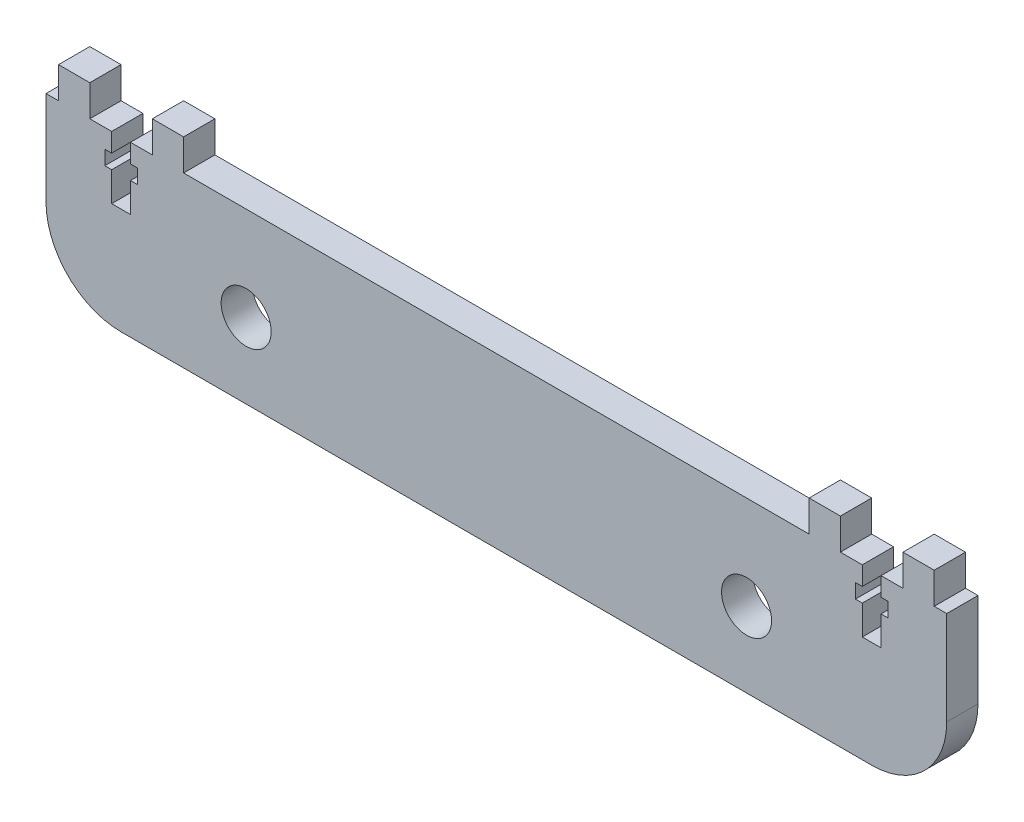
SolidWorks part; units mm, degrees
ref_plane "Front Plane" through (0, 0, 0) normal (0, 0, 1) x (1, 0, 0)
ref_plane "Top Plane" through (0, 0, 0) normal (0, 1, 0) x (1, 0, 0)
ref_plane "Right Plane" through (0, 0, 0) normal (1, 0, 0) x (0, 0, -1)
sketch "Sketch1" plane through (0, 0, 0) normal (0, 0, 1) x (1, 0, 0)
  line L0 (0, 0) -> (0, 77.1281) construction
  line L1 (0, 0) -> (-105.7988, 0) construction
  line L4 (-72, 0) -> (-72, 15)
  line L6 (-72, 15) -> (72, 15)
  line L7 (-60, -12) -> (60, -12)
  line L8 (72, 0) -> (72, 15)
  arc A1 (-72, 0) -> (-60, -12) centre (-60, 0) ccw
  circle A4 centre (-40, 0) radius 4
  circle A5 centre (40, 0) radius 4
  arc A6 (72, 0) -> (60, -12) centre (60, 0) cw
  point P12 (0, -12)
  point P13 (0, 15)
  point P14 (0, -12)
  point P15 (0, 15)
  line B0 (-57.4, 12) -> (-57.4, 9.7)
  line B1 (-61.5, 9.7) -> (-61.5, 5)
  line B2 (-58.5, 5) -> (-58.5, 9.7)
  line B3 (-57.4, 9.7) -> (-58.5, 9.7)
  line B4 (-60, 15) -> (-60, 3.7792) construction
  line B5 (-58.5, 15) -> (-55, 15)
  line B6 (-55, 20) -> (-50, 20)
  line B7 (-50, 20) -> (-50, 15)
  line B8 (-55, 20) -> (-55, 15)
  line B9 (-61.5, 15) -> (-65, 15)
  line B10 (-65, 15) -> (-65, 20)
  line B11 (-65, 20) -> (-70, 20)
  line B12 (-70, 20) -> (-70, 15)
  line B13 (-58.5, 15) -> (-61.5, 15) construction
  line B14 (-61.5, 15) -> (-61.5, 12)
  line B15 (-61.5, 9.7) -> (-62.6, 9.7)
  line B16 (-62.6, 12) -> (-61.5, 12)
  line B17 (-61.5, 5) -> (-58.5, 5)
  line B18 (-58.5, 12) -> (-57.4, 12)
  line B19 (-62.6, 9.7) -> (-62.6, 12)
  line B20 (-58.5, 12) -> (-58.5, 15)
  line B21 (-60, 5) -> (-60, 15) construction
  line B22 (57.4, 12) -> (57.4, 9.7)
  line B23 (61.5, 9.7) -> (61.5, 5)
  line B24 (58.5, 5) -> (58.5, 9.7)
  line B25 (57.4, 9.7) -> (58.5, 9.7)
  line B26 (60, 15) -> (60, 3.7792) construction
  line B27 (58.5, 15) -> (55, 15)
  line B28 (55, 20) -> (50, 20)
  line B29 (50, 20) -> (50, 15)
  line B30 (55, 20) -> (55, 15)
  line B31 (61.5, 15) -> (65, 15)
  line B32 (65, 15) -> (65, 20)
  line B33 (65, 20) -> (70, 20)
  line B34 (70, 20) -> (70, 15)
  line B35 (58.5, 15) -> (61.5, 15) construction
  line B36 (61.5, 15) -> (61.5, 12)
  line B37 (61.5, 9.7) -> (62.6, 9.7)
  line B38 (62.6, 12) -> (61.5, 12)
  line B39 (61.5, 5) -> (58.5, 5)
  line B40 (58.5, 12) -> (57.4, 12)
  line B41 (62.6, 9.7) -> (62.6, 12)
  line B42 (58.5, 12) -> (58.5, 15)
  line B43 (60, 5) -> (60, 15) construction
  dimension "D3" = 12
  dimension "D4" = 12
  dimension "D6" = 8
  dimension "D1" = 60
  dimension "D2" = 40
  dimension "D5" = 15
sketch_block_instance "Insert M3 plots ep 5mm-1"
sketch_block "Insert M3 plots ep 5mm" parameters "D1"=10, "D2"=5, "D3"=5
sketch_block_instance "Decoupe Insert M3-4"
sketch_block "Decoupe Insert M3" parameters "D1"=5.2, "D2"=3, "D3"=2.3, "D4"=3, "D5"=10
sketch_block_instance "Insert M3 plots ep 5mm-4"
extrude "Boss-Extrude2" add sketch "Sketch1" along normal blind 5 contours B40 B42 L6 B20 B18 B0 B3 B2 B17 B1 B15 B19 B16 B14 L4 A1 L7 A6 L8 B36 B38 B41 B37 B23 B39 B24 B25 B22 A4 A5 | B30 B28 B29 L6 | B34 B33 B32 L6 | B11 B12 L6 B10 | B6 B8 L6 B7 region at (0, 1.5588, 0) region at (-67.5, 17.5, 0) region at (67.5, 17.5, 0) region at (-52.5, 17.5, 0) region at (52.5, 17.5, 0)
